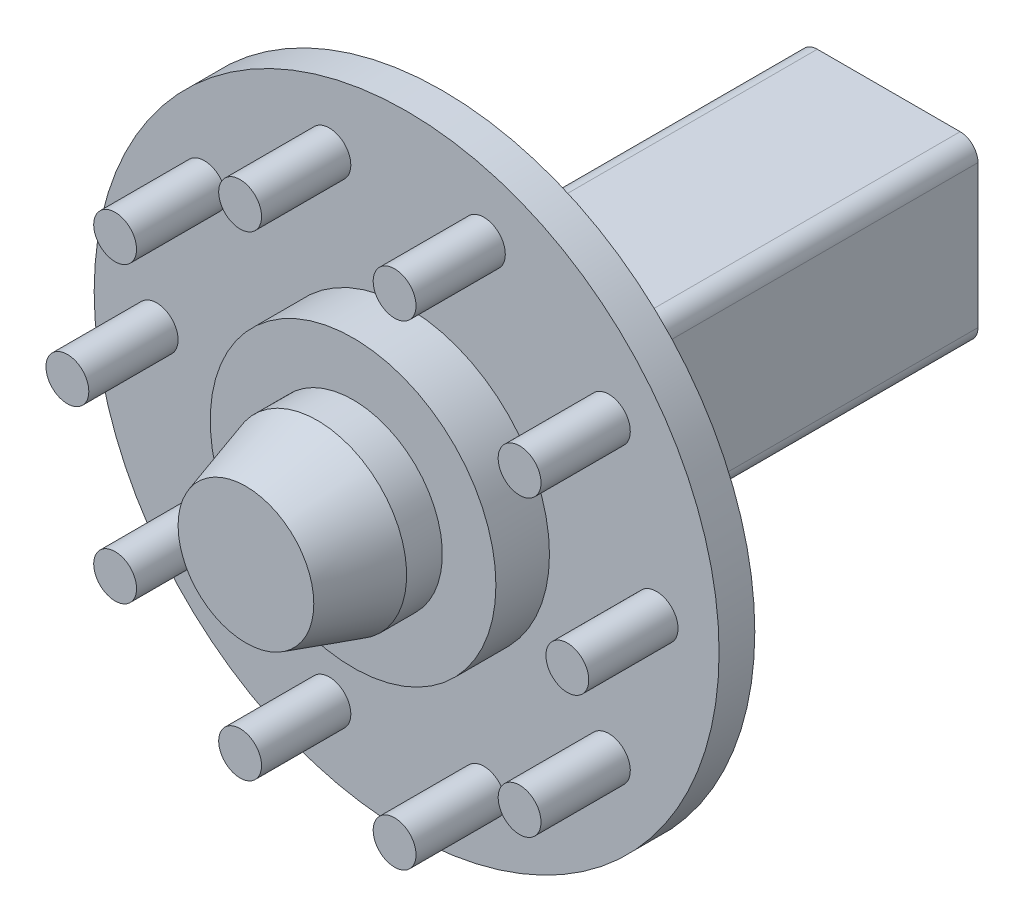
SolidWorks part; units mm, degrees
ref_plane "Front Plane" through (0, 0, 0) normal (0, 0, 1) x (1, 0, 0)
ref_plane "Top Plane" through (0, 0, 0) normal (0, 1, 0) x (1, 0, 0)
ref_plane "Right Plane" through (0, 0, 0) normal (1, 0, 0) x (0, 0, -1)
sketch "Sketch1" plane through (0, 0, 0) normal (0, 0, 1) x (1, 0, 0)
  line L1 (10, 0) -> (90, 0)
  line L2 (0, 10) -> (0, 90)
  line L3 (10, 100) -> (90, 100)
  line L4 (100, 10) -> (100, 90)
  arc A0 (0, 90) -> (10, 100) centre (10, 90) cw
  arc A1 (90, 100) -> (100, 90) centre (90, 90) cw
  arc A2 (90, 0) -> (100, 10) centre (90, 10) ccw
  arc A3 (10, 0) -> (0, 10) centre (10, 10) cw
  point P6 (0, 100)
  point P11 (100, 0)
  point P14 (0, 0)
  dimension "D3" = 10
  dimension "D1" = 100
  dimension "D2" = 100
extrude "Extrude1" add sketch "Sketch1" along normal blind 230
sketch "Sketch2" plane through (0, 0, 230) normal (0, 0, 1) x (1, 0, 0)
  line L0 (0, 90) -> (0, 10) construction
  line L1 (90, 100) -> (10, 100) construction
  circle A0 centre (50, 50) radius 50
  dimension "D3" = 100
  dimension "D1" = 50
  dimension "D2" = 50
extrude "Extrude4" add sketch "Sketch2" along normal blind 20
sketch "Sketch5" plane through (0, 0, 250) normal (0, 0, 1) x (1, 0, 0)
  circle A4 centre (50, 50) radius 175
  dimension "D1" = 350
extrude "Extrude5" add sketch "Sketch5" along normal blind 20
sketch "Sketch6" plane through (0, 0, 270) normal (0, 0, 1) x (1, 0, 0)
  circle A3 centre (50, 50) radius 50
  dimension "D1" = 100
extrude "Extrude6" add sketch "Sketch6" along normal blind 90
chamfer "Chamfer2" distance 40 distance2 12 1 edges at (100, 50, 360) first distance on face at (100, 50, 360)
sketch "Sketch7" plane through (0, 0, 270) normal (0, 0, 1) x (1, 0, 0)
  circle A3 centre (50, 50) radius 80
  dimension "D1" = 160
extrude "Extrude7" add sketch "Sketch7" along normal blind 30
sketch "Sketch8" plane through (0, 0, 270) normal (0, 0, 1) x (1, 0, 0)
  circle A0 centre (-90, 50) radius 12
  circle A2 centre (50, 50) radius 38 construction
  point P4 (50, 50)
  dimension "D2" = 24
  dimension "D1" = 140
extrude "Extrude8" add sketch "Sketch8" along normal blind 50
ref_axis "Axis1" through (50, 50, 320) along (0, 0, 1)
pattern_circular "CirPattern1" count 10 every 36 about axis through (50, 50, 320) along (0, 0, 1) of "Extrude8"
